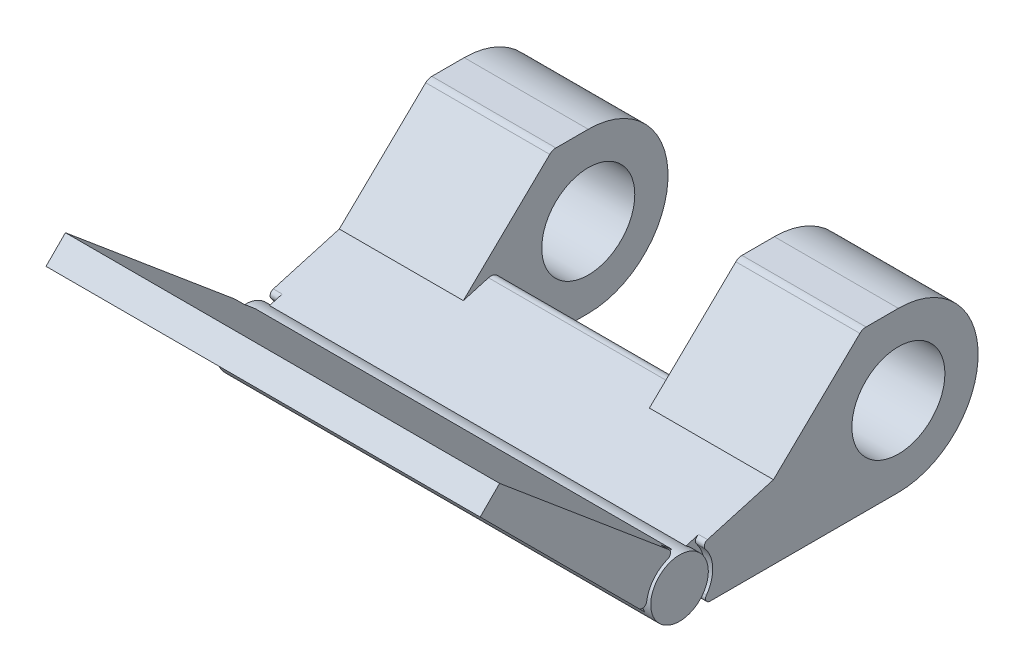
SolidWorks part; units mm, degrees
ref_plane "Front Plane" through (0, 0, 0) normal (0, 0, 1) x (1, 0, 0)
ref_plane "Top Plane" through (0, 0, 0) normal (0, 1, 0) x (1, 0, 0)
ref_plane "Right Plane" through (0, 0, 0) normal (1, 0, 0) x (0, 0, -1)
sketch "Sketch2" plane through (0, 0, 0) normal (1, 0, 0) x (0, 0, -1)
  line L0 (0, 0) -> (-21.2631, 0)
  line L1 (0, 0) -> (0, 18) construction
  line L2 (0, 18) -> (-4.0554, 18)
  line L3 (-4.0554, 18) -> (-14.1, 8.3)
  line L4 (-14.1, 8.3) -> (-21.5434, 6.1656)
  line L5 (-25.8941, 7.3536) -> (-45.008, 23.392)
  line L6 (-45.008, 23.392) -> (-47.2, 21.2)
  line L7 (-47.2, 21.2) -> (-29.2592, 3.2592)
  line L8 (-47.2, 21.2) -> (-27.6616, 1.6616)
  line L9 (-21.2631, 0) -> (-23.45, 0)
  line L10 (-21.5434, 6.1656) -> (-22.9758, 5.7549)
  line L11 (-25.8941, 7.3536) -> (-24.5761, 6.2476)
  arc A0 (0, 0) -> (0, 18) centre (0, 9) ccw
  circle A1 centre (-24.7, 3) radius 3.25
  arc A2 (-21.6674, 0.7941) -> (-21.7932, 5.3691) centre (-24.7, 3) ccw
  circle A3 centre (0, 9) radius 5.25
  arc A4 (-21.7932, 5.3691) -> (-21.6674, 0.7941) centre (-24.7, 3) cw
  arc A5 (-21.5434, 6.1656) -> (-21.7932, 5.3691) centre (-21.4056, 5.685) ccw
  arc A6 (-21.2631, 0) -> (-21.6674, 0.7941) centre (-21.2631, 0.5) cw
  arc A7 (-28.4108, 3.5406) -> (-26.0372, 6.5035) centre (-24.7, 3) cw
  arc A8 (-26.0372, 6.5035) -> (-25.8941, 7.3536) centre (-26.2155, 6.9706) ccw
  arc A9 (-28.4108, 3.5406) -> (-29.2592, 3.2592) centre (-28.9056, 3.6127) cw
  arc A10 (-26.0372, 6.5035) -> (-28.4108, 3.5406) centre (-24.7, 3) ccw
  point P14 (-22.3611, 5.9312)
  point P15 (-24.5761, 6.2476)
  dimension "D1" = 10.5
  dimension "D2" = 18
  dimension "D8" = 6.5
  dimension "D9" = 7.5
  dimension "D11" = 0.5
  dimension "D3" = 0.5
  dimension "D18" = 0.5
  dimension "D19" = 0.5
  dimension "D4" = 152
  dimension "D5" = 16
  dimension "D6" = 24.7
  dimension "D7" = 3
  dimension "D10" = 14.1
  dimension "D12" = 8.3
  dimension "D13" = 3.1
  dimension "D14" = 5
  dimension "D15" = 135
  dimension "D16" = 47.2
  dimension "D17" = 21.2
extrude "Boss-Extrude1" add sketch "Sketch2" against normal blind 14 contours A9 A7 A8 L5 L6 L7 | A1 | L0 L1 A3 L2 L3 L4 A5 A2 A6 | L1 A0 A3 | A7 A9 L8 A1 L11 A8 | L9 A6 A2 A5 L10 A1 region at (0, 6.3808, 9.7602) region at (0, 1.875, -0.2012) region at (0, 0.0665, 22.3565) region at (0, 3, 24.7) region at (0, 2.5125, 28.4083) region at (0, 12.9766, 35.9509)
extrude "Cut-Extrude1" cut sketch "Sketch2<5>" against normal blind 1 contours A7 A9 L8 A1 L11 A8 region at (0, 2.5125, 28.4083)
sketch "Sketch2<5>" plane through (0, 0, 0) normal (1, 0, 0) x (0, 0, -1) same geometry as "Sketch2"
extrude "Cut-Extrude2" cut sketch "Sketch2<6>" against normal blind 1 contours L9 A6 A2 A5 L10 A1 region at (0, 0.0665, 22.3565)
sketch "Sketch2<6>" plane through (0, 0, 0) normal (1, 0, 0) x (0, 0, -1) same geometry as "Sketch2"
sketch "Sketch3" plane through (-14, 0, 0) normal (-1, 0, 0) x (0, 0, 1)
  line L0 (0, 0) -> (0, 14.25) construction
  line L1 (45.008, 23.392) -> (24.5761, 6.2476)
  line L2 (45.008, 23.392) -> (47.2, 21.2)
  line L3 (47.2, 21.2) -> (27.6616, 1.6616)
  line L4 (22.9758, 5.7549) -> (11.2596, 9.1145)
  line L5 (23.45, 0) -> (7.5739, 0)
  line L7 (14.1, 8.3) -> (22.9758, 5.7549) construction
  line L8 (0, 0) -> (23.45, 0) construction
  circle A0 centre (0, 9) radius 5.25 construction
  circle A1 centre (0, 9) radius 5.25
  arc A2 (6.8864, 1.7262) -> (9.9869, 8.2301) centre (0, 9) ccw
  circle A3 centre (24.7, 3) radius 3.25
  arc A4 (9.9869, 8.2301) -> (6.8864, 1.7262) centre (0, 9) cw
  arc A5 (9.9869, 8.2301) -> (11.2596, 9.1145) centre (10.984, 8.1532) cw
  arc A6 (7.5739, 0) -> (6.8864, 1.7262) centre (7.5739, 1) cw
  point P32 (10.0053, 9.4741)
  line M5 (47.2, 21.2) -> (45.008, 23.392)
  line M6 (45.008, 23.392) -> (24.5761, 6.2476)
  arc M7 (24.5761, 6.2476) -> (22.9758, 5.7549) centre (24.7, 3) ccw
  line M8 (22.9758, 5.7549) -> (14.1, 8.3)
  line M12 (0, 0) -> (23.45, 0)
  arc M13 (23.45, 0) -> (27.6616, 1.6616) centre (24.7, 3) ccw
  line M14 (27.6616, 1.6616) -> (47.2, 21.2)
  dimension "D1" = 10.5
  dimension "D2" = 20.0331
  dimension "D3" = 6.5
  dimension "D4" = 1
  dimension "D5" = 1
extrude "Boss-Extrude2" add sketch "Sketch3" along normal blind 9 contours A6 A3 L4 A5 A2 M12 M8 | A3 M7 M13 | A3 M14 M5 M6 region at (-14, 12.7068, 35.6636) region at (-14, 3, 24.7) region at (-14, 3.7232, 14.7638)
extrude "Boss-Extrude3" add sketch "Sketch3<3>" along normal blind 9.5 contours A3 M7 M13 region at (-14, 3, 24.7)
sketch "Sketch3<3>" plane through (-14, 0, 0) normal (-1, 0, 0) x (0, 0, 1) same geometry as "Sketch3"
fillet "Fillet1" radius 1 1 edges at (-7, 18, 4.0554)
mirror "Mirror1" about plane through (0, 0, 0) normal (1, 0, 0) of "Cut-Extrude1", "Cut-Extrude2", "Boss-Extrude2", "Boss-Extrude3", "Fillet1", "Boss-Extrude1"
sketch "Sketch4" plane through (0, -8.4351, 7.0779) normal (0, 0.766, -0.6428) x (1, 0, 0)
  line L0 (0, 0) -> (0, -53.2286)
  line L1 (0, -53.2286) -> (-37.9231, -53.2286)
  line L2 (-37.9231, -53.2286) -> (-37.9231, 7.1355)
  line L3 (-37.9231, 7.1355) -> (0, 7.1355)
  line L4 (0, 7.1355) -> (0, 0)
extrude "Cut-Extrude3" cut sketch "Sketch4" against normal through all both and the other way through all
sketch "Sketch7" plane through (23, 0, 0) normal (1, 0, 0) x (0, 0, -1)
  line L0 (-22.9758, 5.7549) -> (-11.2596, 9.1145)
  line L1 (-23.45, 0) -> (-7.5739, 0)
  line L2 (-24.5761, 6.2476) -> (-45.008, 23.392)
  line L3 (-45.008, 23.392) -> (-47.2, 21.2)
  line L4 (-47.2, 21.2) -> (-27.6616, 1.6616)
  circle A0 centre (-7.5739, 1) radius 1
  circle A1 centre (0, 9) radius 10.0165
  circle A2 centre (-10.984, 8.1532) radius 1
  circle A3 centre (-24.7, 3) radius 3.25
  arc M1 (-22.9758, 5.7549) -> (-23.45, 0) centre (-24.7, 3) cw
  line M2 (-23.45, 0) -> (-7.5739, 0)
  arc M3 (-7.5739, 0) -> (-6.8864, 1.7262) centre (-7.5739, 1) ccw
  arc M4 (-6.8864, 1.7262) -> (-9.9869, 8.2301) centre (0, 9) cw
  arc M5 (-9.9869, 8.2301) -> (-11.2596, 9.1145) centre (-10.984, 8.1532) ccw
  line M6 (-11.2596, 9.1145) -> (-22.9758, 5.7549)
extrude "Boss-Extrude4" add sketch "Sketch7" along normal blind 1.5 contours A3 L2 L3 L4 | A3 M1 | A2 A0 M6 M1 M2 M4 | A2 M5 | A0 M3 region at (23, 3.6689, 15.1125) region at (23, 3, 24.7) region at (23, 8.1532, 10.984) region at (23, 12.7068, 35.6636) region at (23, 1, 7.5739)
mirror "Mirror14" about plane through (24.5, 0, 0) normal (1, 0, 0) of bodies 108
